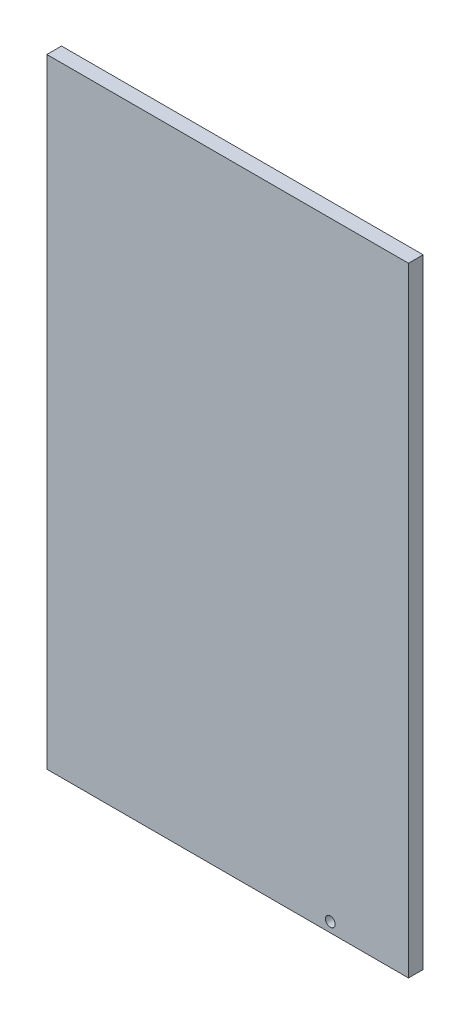
SolidWorks part; units mm, degrees
material "Perspex (TM) GS Acrylic Cast Sheet"
ref_plane "Front Plane" through (0, 0, 0) normal (0, 0, 1) x (1, 0, 0)
ref_plane "Top Plane" through (0, 0, 0) normal (0, 1, 0) x (1, 0, 0)
ref_plane "Right Plane" through (0, 0, 0) normal (1, 0, 0) x (0, 0, -1)
sketch "Sketch1" plane through (0, 0, 0) normal (0, 0, 1) x (1, 0, 0)
  line L1 (-111, -190) -> (111, -190)
  line L2 (-111, -190) -> (-111, 190)
  line L3 (-111, 190) -> (111, 190)
  line L4 (111, -190) -> (111, 190)
  line L5 (-111, -190) -> (111, 190) construction
  line L6 (-111, 190) -> (111, -190) construction
  point P0 (0, 0)
  dimension "D1" = 222
  dimension "D2" = 380
extrude "Boss-Extrude1" add sketch "Sketch1" along normal blind 9
sketch "Sketch2" plane through (0, 0, 9) normal (0, 0, 1) x (1, 0, 0)
  line L0 (111, -190) -> (111, 190) construction
  line L1 (-111, -190) -> (111, -190) construction
  circle A0 centre (63, -184) radius 3
  dimension "D1" = 6
  dimension "D2" = 48
  dimension "D3" = 6
extrude "Cut-Extrude1" cut sketch "Sketch2" against normal through all
sketch "Sketch4" [suppressed] plane through (0, 0, 0) normal (0, 0, -1) x (-1, 0, 0)
  circle A0 centre (-30, -170) radius 5.5
  circle A1 centre (-90, -170) radius 5.5
  circle A2 centre (30, -170) radius 5.5
  circle A3 centre (90, -170) radius 5.5
  dimension "D1" = 11
extrude "Cut-Extrude2" [suppressed] cut sketch "Sketch4" against normal through all
equation "\"PCLength\"= 145mm'Length across I/O from PS to GPU"
equation "\"PCWidth\"= 340mm'Distance of longest part parallel to GPU(ussually GPU)"
equation "\"PCHeight\"= 180mm'Tallest point with mobo laying flat"
equation "\"WallThickness\"= 9mm'Thickness of each outer tank wall"
equation "\"ThermoBarrierThickness\"= 6mm'Thickness of barrier between hot side and cold side"
equation "\"HotSideGap\"= 36mm'Space in the hot side for a pump"
equation "\"PCClearance\"= 40mm'Clearance from top of tank to top of PC"
equation "\"RadiatorHeight\"= 277.37mm'Final Height from ground of radiators"
equation "\"D1@Sketch1\"=\"PCHeight\" + \"ThermoBarrierThickness\" + \"HotSideGap\""
equation "\"D2@Sketch1\"=\"PCWidth\" + \"PCClearance\""
equation "\"D1@Boss-Extrude1\"=\"WallThickness\""
equation "\"D2@Sketch2\"=\"HotSideGap\" + \"ThermoBarrierThickness\" + 6"
